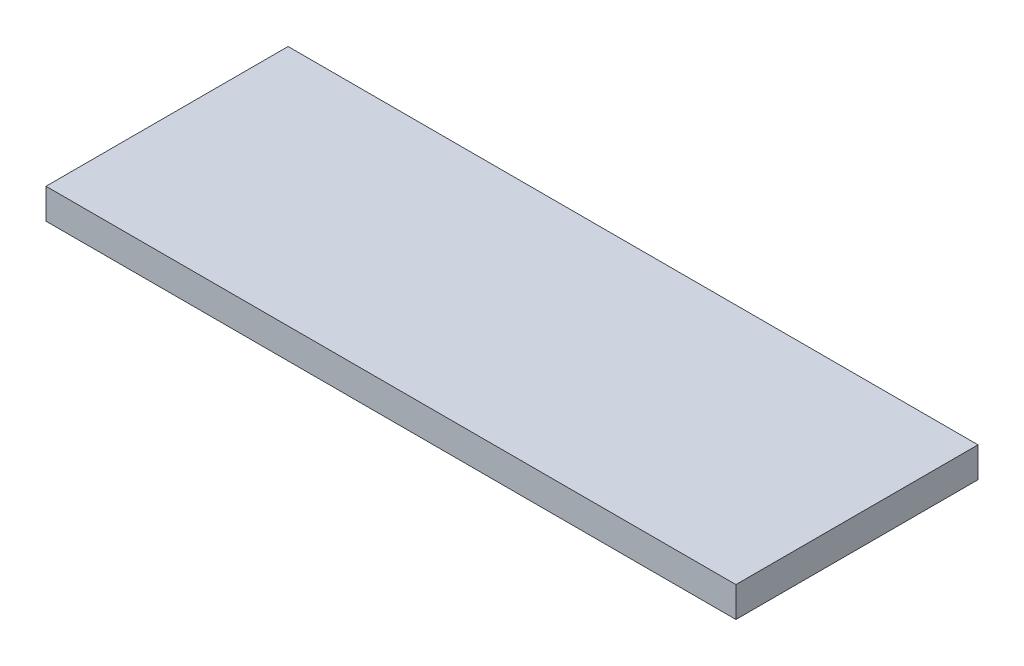
SolidWorks part; units mm, degrees
ref_plane "正面" through (0, 0, 0) normal (0, 0, 1) x (1, 0, 0)
ref_plane "平面" through (0, 0, 0) normal (0, 1, 0) x (1, 0, 0)
ref_plane "右側面" through (0, 0, 0) normal (1, 0, 0) x (0, 0, -1)
sketch "ｽｹｯﾁ1" plane through (0, 0, 0) normal (0, 1, 0) x (1, 0, 0)
  line L1 (-57, 20) -> (57, 20)
  line L2 (-57, 20) -> (-57, -20)
  line L3 (-57, -20) -> (57, -20)
  line L4 (57, 20) -> (57, -20)
  line L5 (-57, 20) -> (57, -20) construction
  line L6 (-57, -20) -> (57, 20) construction
  point P0 (0, 0)
  dimension "D1" = 114
  dimension "D2" = 40
extrude "ﾎﾞｽ - 押し出し1" add sketch "ｽｹｯﾁ1" along normal blind 5
